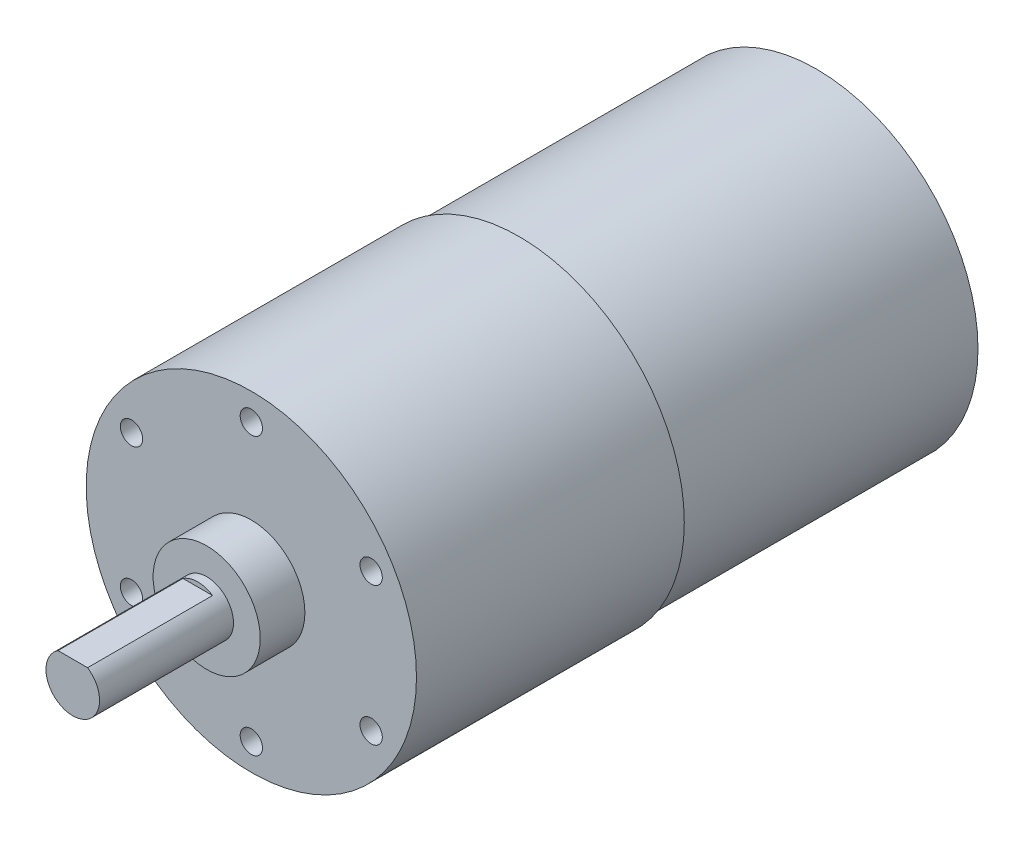
SolidWorks part; units mm, degrees
ref_plane "Front Plane" through (0, 0, 0) normal (0, 0, 1) x (1, 0, 0)
ref_plane "Top Plane" through (0, 0, 0) normal (0, 1, 0) x (1, 0, 0)
ref_plane "Right Plane" through (0, 0, 0) normal (1, 0, 0) x (0, 0, -1)
sketch "Sketch1" plane through (0, 0, 0) normal (0, 0, 1) x (1, 0, 0)
  circle A0 centre (0, 0) radius 18.5
  dimension "D1" = 37
extrude "Boss-Extrude1" add sketch "Sketch1" along normal blind 30
sketch "Sketch2" plane through (0, 0, 0) normal (0, 0, -1) x (-1, 0, 0)
  circle A0 centre (0, 0) radius 18.1
  dimension "D1" = 36.2
extrude "Boss-Extrude2" add sketch "Sketch2" along normal blind 33.3
sketch "Sketch3" plane through (0, 0, 30) normal (0, 0, 1) x (1, 0, 0)
  circle A0 centre (0, 0) radius 6
  dimension "D1" = 12
extrude "Boss-Extrude3" add sketch "Sketch3" along normal blind 5
sketch "Sketch4" plane through (0, 0, 35) normal (0, 0, 1) x (1, 0, 0)
  circle A0 centre (0, 0) radius 3
  dimension "D1" = 6
extrude "Boss-Extrude4" add sketch "Sketch4" along normal blind 1
sketch "Sketch5" plane through (0, 0, 36) normal (0, 0, 1) x (1, 0, 0)
  line L1 (-1.6583, 2.5) -> (1.6583, 2.5)
  arc A0 (-1.6583, 2.5) -> (1.6583, 2.5) centre (0, 0) ccw
  circle A1 centre (0, 0) radius 3 construction
  point P5 (0, 2.5)
  point P6 (0, -3)
  dimension "D1" = 5.5
extrude "Boss-Extrude5" add sketch "Sketch5" along normal blind 14
sketch "Sketch10" plane through (0, 0, 30) normal (0, 0, 1) x (1, 0, 0)
  point P0 (0, 0)
hole_wizard "M3x0.5 Tapped Hole1" positions "Sketch11" profile "Sketch12" tap size "M3x0.5" standard "ANSI Metric"
sketch "Sketch11" plane through (0, 0, 30) normal (0, 0, 1) x (1, 0, 0)
  line L0 (0, 0) -> (0, 15.5) construction
  point P0 (0, 15.5)
  point P8 (13.4234, 7.75)
  point P9 (13.4234, -7.75)
  point P10 (0, -15.5)
  point P11 (-13.4234, -7.75)
  point P12 (-13.4234, 7.75)
  dimension "D3" = 15.5
  dimension "D2" = 6
sketch "Sketch12" plane through (0, 15.5, 30) normal (1, 0, 0) x (0, -1, 0)
  line L0 (0, 0) -> (0, 6.7511)
  line L1 (0, 6.7511) -> (1.25, 6)
  line L2 (1.25, 6) -> (1.25, 0)
  line L5 (1.25, 0) -> (0, 0)
  line L10 (0, 6.7511) -> (-1.25, 6) construction
  line L11 (0, -6.35) -> (0, 107.95) construction
  dimension "Tap Drill Dia." = 2.5
  dimension "Tap Drill Depth" = 6
  dimension "Drill Angle" = 118
cosmetic thread "Hole Thread8" parameters "D1"=6, "D2"=3
cosmetic thread "Hole Thread9" parameters "D1"=6, "D2"=3
cosmetic thread "Hole Thread10" parameters "D1"=6, "D2"=3
cosmetic thread "Hole Thread11" parameters "D1"=6, "D2"=3
cosmetic thread "Hole Thread12" parameters "D1"=6, "D2"=3
cosmetic thread "Hole Thread13" parameters "D1"=6, "D2"=3
equation "\"PCB Width\"= 1940mil"
equation "\"PCB Height\"= 2210mil"
equation "\"PCB Thickness\"= 63mil"
equation "\"Motor Body Front Diameter\"= 37mm"
equation "\"Motor Body Front Length\"= 30mm"
equation "\"Motor Bearing Length\"= 5mm"
equation "\"Motor Body Back Length\"= 33.3mm"
equation "\"Motor PCR\"= 31mm / 2"
equation "\"Large PVC Fittings Wall Thickness\"= 15in / 64"
equation "\"Large PVC Pipe Outer Diameter\"= 3.5in"
equation "\"Box Width\"= 2 * \"Motor Bearing Length\" + \"Motor Body Front Length\" + \"Motor Body Back Length\" + 0.5in"
equation "\"Box Hole Center to Edge Distance\"= 150mil"
equation "\"Box Ceiling and Floor Thickness\"= 2 * \"Box Hole Center to Edge Distance\""
equation "\"Box Height\"= 2 * \"Box Ceiling and Floor Thickness\" + \"PCB Height\" + 0.5in"
equation "\"Box Back Depth\"= \"Large PVC Fittings Wall Thickness\" + \"Large PVC Pipe Outer Diameter\" / 2 + \"Motor Body Front Diameter\" / 2"
equation "\"D1@Sketch1\"=\"Motor Body Front Diameter\""
equation "\"D1@Boss-Extrude1\"=\"Motor Body Front Length\""
equation "\"D1@Boss-Extrude2\"=\"Motor Body Back Length\""
equation "\"D1@Boss-Extrude3\"=\"Motor Bearing Length\""
equation "\"D3@Sketch11\"=\"Motor PCR\""
